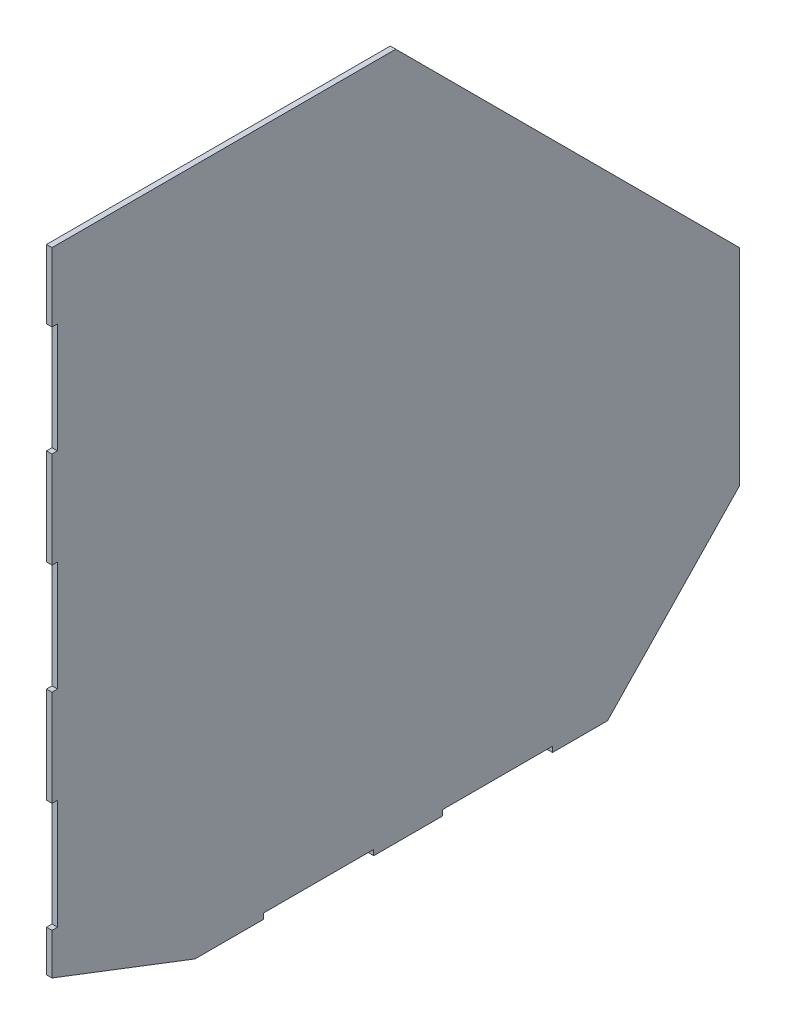
SolidWorks part; units mm, degrees
material "ABS PC"
ref_plane "Спереди" through (0, 0, 0) normal (0, 0, 1) x (1, 0, 0)
ref_plane "Сверху" through (0, 0, 0) normal (0, 1, 0) x (1, 0, 0)
ref_plane "Справа" through (0, 0, 0) normal (1, 0, 0) x (0, 0, -1)
sketch "Sketch1" plane through (0, 0, 0) normal (1, 0, 0) x (0, 0, -1)
  line L1 (0, 250) -> (125, 250)
  line L2 (125, 250) -> (250, 125)
  line L3 (250, 125) -> (250, 50)
  line L4 (202, 0) -> (182, 0)
  line L5 (0, 35) -> (2, 35)
  line L6 (2, 35) -> (2, 75)
  line L7 (2, 75) -> (0, 75)
  line L8 (0, 110) -> (2, 110)
  line L9 (2, 110) -> (2, 150)
  line L10 (2, 150) -> (0, 150)
  line L11 (0, 185) -> (2, 185)
  line L12 (2, 185) -> (2, 225)
  line L13 (2, 225) -> (0, 225)
  line L14 (0, 75) -> (0, 110)
  line L15 (0, 150) -> (0, 185)
  line L16 (0, 225) -> (0, 250)
  line L17 (250, 50) -> (202, 0)
  line L18 (0, 20) -> (52, 0)
  line L19 (0, 35) -> (0, 20)
  line L20 (77, 0) -> (77, 2)
  line L21 (77, 2) -> (117, 2)
  line L22 (117, 2) -> (117, 0)
  line L23 (142, 0) -> (142, 2)
  line L24 (142, 2) -> (182, 2)
  line L25 (182, 2) -> (182, 0)
  line L26 (77, 0) -> (52, 0)
  line L27 (142, 0) -> (117, 0)
  point P0 (0, 0)
  dimension "D2" = 125
  dimension "D3" = 125
  dimension "D4" = 250
  dimension "D5" = 2
  dimension "D6" = 35
  dimension "D7" = 110
  dimension "D8" = 185
  dimension "D9" = 40
  dimension "D10" = 48
  dimension "D11" = 50
  dimension "D12" = 20
  dimension "D13" = 250
  dimension "D14" = 52
  dimension "D15" = 117
  dimension "D16" = 182
extrude "Boss-Extrude1" add sketch "Sketch1" along normal blind 2
